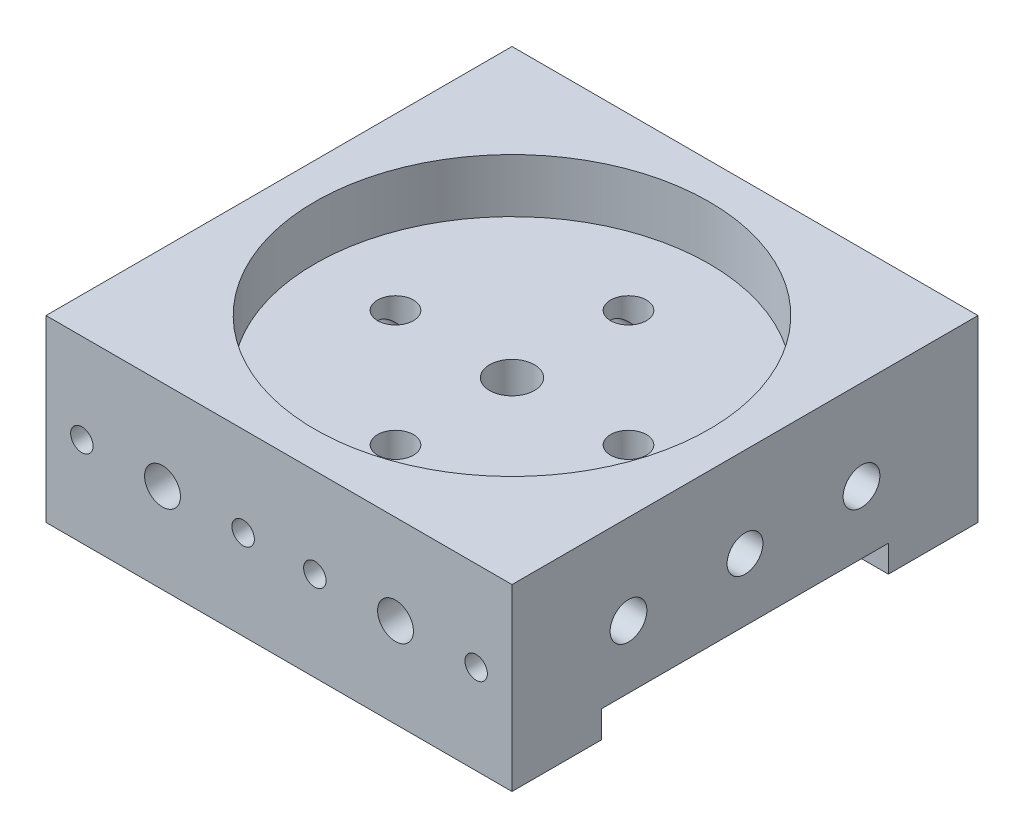
SolidWorks part; units mm, degrees
ref_plane "Front Plane" through (0, 0, 0) normal (0, 0, 1) x (1, 0, 0)
ref_plane "Top Plane" through (0, 0, 0) normal (0, 1, 0) x (1, 0, 0)
ref_plane "Right Plane" through (0, 0, 0) normal (1, 0, 0) x (0, 0, -1)
sketch "Base Block Sketch" plane through (0, 0, 0) normal (0, 1, 0) x (1, 0, 0)
  line L1 (-13, -13) -> (13, -13)
  line L2 (-13, -13) -> (-13, 13)
  line L3 (-13, 13) -> (13, 13)
  line L4 (13, -13) -> (13, 13)
  line L5 (-13, -13) -> (13, 13) construction
  line L6 (-13, 13) -> (13, -13) construction
  point P0 (0, 0)
  dimension "D2" = 13
extrude "Base Block Extrude" add sketch "Base Block Sketch" along normal blind 10
sketch "Top Circular Cut Sketch" plane through (0, 0, 0) normal (0, 1, 0) x (1, 0, 0)
  circle A0 centre (0, 0) radius 11
  dimension "D1" = 22
extrude "Top Circular Cut" cut sketch "Top Circular Cut Sketch" against normal blind 3 from surface starting at face at (0, 10, 0)
sketch "Bottom Slot Sketch" plane through (0, 0, 0) normal (0, 1, 0) x (1, 0, 0)
  line L0 (13, -13) -> (13, 13) construction
  line L1 (-13, -8) -> (13, -8)
  line L2 (-13, -8) -> (-13, 8)
  line L3 (-13, 8) -> (13, 8)
  line L4 (13, -8) -> (13, 8)
  line L5 (-13, -8) -> (13, 8) construction
  line L6 (-13, 8) -> (13, -8) construction
  point P0 (0, 0)
  dimension "D1" = 16
extrude "Bottom Slot Cut" cut sketch "Bottom Slot Sketch" along normal blind 1.5
sketch "3 Large Hole Positions Right Plane" plane through (0, 0, 0) normal (1, 0, 0) x (0, 0, -1)
  line L0 (-13, 10) -> (-13, 0) construction
  line L1 (-13, 10) -> (13, 10) construction
  point P0 (-6.5, 5)
  point P1 (0, 5)
  point P2 (6.5, 5)
  dimension "D1" = 13
  dimension "D2" = 13
  dimension "D3" = 5
  dimension "D4" = 6.5
sketch "6 Hole Positions Front Plane" plane through (0, 0, 0) normal (0, 0, 1) x (1, 0, 0)
  line L0 (-13, 0) -> (13, 0) construction
  line L1 (13, 10) -> (13, 0) construction
  line L2 (-13, 10) -> (-13, 0) construction
  point P0 (-11, 5)
  point P1 (-6.5, 5)
  point P2 (-2, 5)
  point P3 (2, 5)
  point P4 (6.5, 5)
  point P5 (11, 5)
  dimension "D1" = 5
  dimension "D2" = 9
  dimension "D3" = 9
  dimension "D4" = 6.5
  dimension "D5" = 6.5
  dimension "D6" = 4.5
  dimension "D7" = 4.5
sketch "5 Hole Positions in Circle Top Plane" plane through (0, 0, 0) normal (0, 1, 0) x (1, 0, 0)
  point P0 (0, 0)
  point P1 (6.5, 0)
  point P3 (-6.5, 0)
  point P5 (0, 6.5)
  point P6 (0, -6.5)
  dimension "D1" = 13
  dimension "D2" = 13
  dimension "D3" = 6.5
  dimension "D4" = 6.5
hole_wizard "M1.6x0.35 Tapped Hole3" positions "Sketch47" profile "Sketch48" tap size "M1.6x0.35" standard "ANSI Metric"
sketch "Sketch47" plane through (0, 0, 13) normal (0, 0, 1) x (1, 0, 0)
  point P0 (-11, 5)
  point P3 (-2, 5)
  point P6 (2, 5)
  point P9 (11, 5)
sketch "Sketch48" plane through (-11, 5, 13) normal (1, 0, 0) x (0, -1, 0)
  line L0 (0, 0) -> (0, 4.3755)
  line L1 (0, 4.3755) -> (0.625, 4)
  line L2 (0.625, 4) -> (0.625, 0)
  line L5 (0.625, 0) -> (0, 0)
  line L10 (0, 4.3755) -> (-0.625, 4) construction
  line L11 (0, -6.35) -> (0, 107.95) construction
  dimension "Tap Drill Dia." = 1.25
  dimension "Tap Drill Depth" = 4
  dimension "Drill Angle" = 118
cosmetic thread "Hole Thread6" parameters "D1"=3.2, "D2"=1.6
cosmetic thread "Hole Thread7" parameters "D1"=3.2, "D2"=1.6
cosmetic thread "Hole Thread8" parameters "D1"=3.2, "D2"=1.6
cosmetic thread "Hole Thread9" parameters "D1"=3.2, "D2"=1.6
hole_wizard "M1.6x0.35 Tapped Hole4" positions "Sketch49" profile "Sketch50" tap size "M1.6x0.35" standard "ANSI Metric"
sketch "Sketch49" plane through (0, 0, -13) normal (0, 0, -1) x (-1, 0, 0)
  point P0 (-11, 5)
  point P3 (-2, 5)
  point P6 (2, 5)
  point P9 (11, 5)
sketch "Sketch50" plane through (11, 5, -13) normal (1, 0, 0) x (0, 1, 0)
  line L0 (0, 0) -> (0, 4.3755)
  line L1 (0, 4.3755) -> (0.625, 4)
  line L2 (0.625, 4) -> (0.625, 0)
  line L5 (0.625, 0) -> (0, 0)
  line L10 (0, 4.3755) -> (-0.625, 4) construction
  line L11 (0, -6.35) -> (0, 107.95) construction
  dimension "Tap Drill Dia." = 1.25
  dimension "Tap Drill Depth" = 4
  dimension "Drill Angle" = 118
cosmetic thread "Hole Thread10" parameters "D1"=3.2, "D2"=1.6
cosmetic thread "Hole Thread11" parameters "D1"=3.2, "D2"=1.6
cosmetic thread "Hole Thread12" parameters "D1"=3.2, "D2"=1.6
cosmetic thread "Hole Thread13" parameters "D1"=3.2, "D2"=1.6
hole_wizard "Ø2.0 (2) Diameter Hole1" positions "Sketch16" profile "Sketch17" hole size "Ø2.0" standard "ANSI Metric"
sketch "Sketch16" plane through (0, 0, 13) normal (0, 0, 1) x (1, 0, 0)
  point P0 (-6.5, 5)
  point P3 (6.5, 5)
sketch "Sketch17" plane through (-6.5, 5, 13) normal (1, 0, 0) x (0, -1, 0)
  line L0 (0, 0) -> (0, 8.6009)
  line L1 (0, 8.6009) -> (1, 8)
  line L2 (1, 8) -> (1, 0)
  line L5 (1, 0) -> (0, 0)
  line L10 (0, 8.6009) -> (-1, 8) construction
  line L11 (0, -6.35) -> (0, 107.95) construction
  dimension "Hole Dia." = 2
  dimension "Hole Depth" = 8
  dimension "Drill Angle" = 118
hole_wizard "Ø2.0 (2) Diameter Hole2" positions "Sketch18" profile "Sketch19" hole size "Ø2.0" standard "ANSI Metric"
sketch "Sketch18" plane through (0, 0, -13) normal (0, 0, -1) x (-1, 0, 0)
  point P0 (-6.5, 5)
  point P3 (6.5, 5)
sketch "Sketch19" plane through (6.5, 5, -13) normal (1, 0, 0) x (0, 1, 0)
  line L0 (0, 0) -> (0, 8.6009)
  line L1 (0, 8.6009) -> (1, 8)
  line L2 (1, 8) -> (1, 0)
  line L5 (1, 0) -> (0, 0)
  line L10 (0, 8.6009) -> (-1, 8) construction
  line L11 (0, -6.35) -> (0, 107.95) construction
  dimension "Hole Dia." = 2
  dimension "Hole Depth" = 8
  dimension "Drill Angle" = 118
hole_wizard "Ø2.0 (2) Diameter Hole11" positions "Sketch39" profile "Sketch40" hole size "Ø2.0" standard "ANSI Metric" end condition through all
sketch "Sketch39" plane through (0, 7, 0) normal (0, 1, 0) x (1, 0, 0)
  point P0 (-6.5, 0)
  point P3 (0, -6.5)
  point P6 (6.5, 0)
  point P9 (0, 6.5)
sketch "Sketch40" plane through (-6.5, 7, 0) normal (1, 0, 0) x (0, 0, 1)
  line L0 (0, 0) -> (0, 7)
  line L1 (0, 7) -> (1, 7)
  line L2 (1, 7) -> (1, 0)
  line L5 (1, 0) -> (0, 0)
  line L11 (0, -6.35) -> (0, 107.95) construction
  dimension "Thru Hole Dia." = 2
  dimension "Thru Hole Depth" = 7
hole_wizard "M3x0.5 Tapped Hole1" positions "Sketch41" profile "Sketch42" tap size "M3x0.5" standard "ANSI Metric"
sketch "Sketch41" plane through (0, 7, 0) normal (0, 1, 0) x (1, 0, 0)
  point P0 (0, 0)
sketch "Sketch42" plane through (0, 7, 0) normal (1, 0, 0) x (0, 0, 1)
  line L0 (0, 0) -> (0, 4.7511)
  line L1 (0, 4.7511) -> (1.25, 4)
  line L2 (1.25, 4) -> (1.25, 0)
  line L5 (1.25, 0) -> (0, 0)
  line L10 (0, 4.7511) -> (-1.25, 4) construction
  line L11 (0, -6.35) -> (0, 107.95) construction
  dimension "Tap Drill Dia." = 2.5
  dimension "Tap Drill Depth" = 4
  dimension "Drill Angle" = 118
cosmetic thread "Hole Thread1" parameters "D1"=6, "D2"=3
hole_wizard "M2.5x0.45 Tapped Hole2" positions "Sketch51" profile "Sketch52" tap size "M2.5x0.45" standard "ANSI Metric"
sketch "Sketch51" plane through (13, 0, 0) normal (1, 0, 0) x (0, 0, -1)
  point P0 (-6.5, 5)
sketch "Sketch52" plane through (13, 5, 6.5) normal (0, 1, 0) x (0, 0, -1)
  line L0 (0, 0) -> (0, 13.6159)
  line L1 (0, 13.6159) -> (1.025, 13)
  line L2 (1.025, 13) -> (1.025, 0)
  line L5 (1.025, 0) -> (0, 0)
  line L10 (0, 13.6159) -> (-1.025, 13) construction
  line L11 (0, -6.35) -> (0, 107.95) construction
  dimension "Tap Drill Dia." = 2.05
  dimension "Tap Drill Depth" = 13
  dimension "Drill Angle" = 118
cosmetic thread "Hole Thread14" parameters "D1"=5, "D2"=2.5
hole_wizard "M2.5x0.45 Tapped Hole3" positions "Sketch53" profile "Sketch54" tap size "M2.5x0.45" standard "ANSI Metric"
sketch "Sketch53" plane through (-13, 0, 0) normal (-1, 0, 0) x (0, 0, 1)
  point P0 (-6.5, 5)
sketch "Sketch54" plane through (-13, 5, -6.5) normal (0, 1, 0) x (0, 0, 1)
  line L0 (0, 0) -> (0, 13.6159)
  line L1 (0, 13.6159) -> (1.025, 13)
  line L2 (1.025, 13) -> (1.025, 0)
  line L5 (1.025, 0) -> (0, 0)
  line L10 (0, 13.6159) -> (-1.025, 13) construction
  line L11 (0, -6.35) -> (0, 107.95) construction
  dimension "Tap Drill Dia." = 2.05
  dimension "Tap Drill Depth" = 13
  dimension "Drill Angle" = 118
cosmetic thread "Hole Thread15" parameters "D1"=5, "D2"=2.5
hole_wizard "M2.5x0.45 Tapped Hole4" positions "Sketch55" profile "Sketch56" tap size "M2.5x0.45" standard "ANSI Metric"
sketch "Sketch55" plane through (13, 0, 0) normal (1, 0, 0) x (0, 0, -1)
  point P0 (6.5, 5)
sketch "Sketch56" plane through (13, 5, -6.5) normal (0, 1, 0) x (0, 0, -1)
  line L0 (0, 0) -> (0, 7.1159)
  line L1 (0, 7.1159) -> (1.025, 6.5)
  line L2 (1.025, 6.5) -> (1.025, 0)
  line L5 (1.025, 0) -> (0, 0)
  line L10 (0, 7.1159) -> (-1.025, 6.5) construction
  line L11 (0, -6.35) -> (0, 107.95) construction
  dimension "Tap Drill Dia." = 2.05
  dimension "Tap Drill Depth" = 6.5
  dimension "Drill Angle" = 118
cosmetic thread "Hole Thread16" parameters "D1"=5, "D2"=2.5
hole_wizard "M2.5x0.45 Tapped Hole5" positions "Sketch57" profile "Sketch58" tap size "M2.5x0.45" standard "ANSI Metric"
sketch "Sketch57" plane through (-13, 0, 0) normal (-1, 0, 0) x (0, 0, 1)
  point P0 (6.5, 5)
sketch "Sketch58" plane through (-13, 5, 6.5) normal (0, 1, 0) x (0, 0, 1)
  line L0 (0, 0) -> (0, 7.1159)
  line L1 (0, 7.1159) -> (1.025, 6.5)
  line L2 (1.025, 6.5) -> (1.025, 0)
  line L5 (1.025, 0) -> (0, 0)
  line L10 (0, 7.1159) -> (-1.025, 6.5) construction
  line L11 (0, -6.35) -> (0, 107.95) construction
  dimension "Tap Drill Dia." = 2.05
  dimension "Tap Drill Depth" = 6.5
  dimension "Drill Angle" = 118
cosmetic thread "Hole Thread17" parameters "D1"=5, "D2"=2.5
hole_wizard "Ø2.0 (2) Diameter Hole5" positions "Sketch26" profile "Sketch27" hole size "Ø2.0" standard "ANSI Metric"
sketch "Sketch26" plane through (13, 0, 0) normal (1, 0, 0) x (0, 0, -1)
  point P0 (-6.5, 5)
  point P3 (0, 5)
sketch "Sketch27" plane through (13, 5, 6.5) normal (0, 1, 0) x (0, 0, -1)
  line L0 (0, 0) -> (0, 7.1009)
  line L1 (0, 7.1009) -> (1, 6.5)
  line L2 (1, 6.5) -> (1, 0)
  line L5 (1, 0) -> (0, 0)
  line L10 (0, 7.1009) -> (-1, 6.5) construction
  line L11 (0, -6.35) -> (0, 107.95) construction
  dimension "Hole Dia." = 2
  dimension "Hole Depth" = 6.5
  dimension "Drill Angle" = 118
hole_wizard "Ø2.0 (2) Diameter Hole6" positions "Sketch28" profile "Sketch29" hole size "Ø2.0" standard "ANSI Metric"
sketch "Sketch28" plane through (-13, 0, 0) normal (-1, 0, 0) x (0, 0, 1)
  point P0 (-6.5, 5)
  point P3 (0, 5)
sketch "Sketch29" plane through (-13, 5, -6.5) normal (0, 1, 0) x (0, 0, 1)
  line L0 (0, 0) -> (0, 7.1009)
  line L1 (0, 7.1009) -> (1, 6.5)
  line L2 (1, 6.5) -> (1, 0)
  line L5 (1, 0) -> (0, 0)
  line L10 (0, 7.1009) -> (-1, 6.5) construction
  line L11 (0, -6.35) -> (0, 107.95) construction
  dimension "Hole Dia." = 2
  dimension "Hole Depth" = 6.5
  dimension "Drill Angle" = 118
sketch "Bottom Plate Securing Holes" plane through (0, 0, 0) normal (0, 1, 0) x (1, 0, 0)
  line L0 (13, 8) -> (-13, 8) construction
  line L1 (-3, 4) -> (3, 4) construction
  line L2 (-3, 4) -> (-3, -4) construction
  line L3 (-3, -4) -> (3, -4) construction
  line L4 (3, 4) -> (3, -4) construction
  line L5 (-3, 4) -> (3, -4) construction
  line L6 (-3, -4) -> (3, 4) construction
  line L7 (13, 8) -> (13, 13) construction
  point P0 (0, 0)
  dimension "D1" = 4
  dimension "D2" = 10
hole_wizard "M1.6x0.35 Tapped Hole5" positions "Sketch65" profile "Sketch66" tap size "M1.6x0.35" standard "ANSI Metric"
sketch "Sketch65" plane through (0, 1.5, 0) normal (0, -1, 0) x (-1, 0, 0)
  point P0 (3, 4)
  point P3 (-3, -4)
sketch "Sketch66" plane through (-3, 1.5, -4) normal (1, 0, 0) x (0, 0, -1)
  line L0 (0, 0) -> (0, 3.3755)
  line L1 (0, 3.3755) -> (0.625, 3)
  line L2 (0.625, 3) -> (0.625, 0)
  line L5 (0.625, 0) -> (0, 0)
  line L10 (0, 3.3755) -> (-0.625, 3) construction
  line L11 (0, -6.35) -> (0, 107.95) construction
  dimension "Tap Drill Dia." = 1.25
  dimension "Tap Drill Depth" = 3
  dimension "Drill Angle" = 118
cosmetic thread "Hole Thread18" parameters "D1"=3.2, "D2"=1.6
cosmetic thread "Hole Thread19" parameters "D1"=3.2, "D2"=1.6
sketch "4 Bottom Hole Positions" plane through (0, 0, 0) normal (0, 1, 0) x (1, 0, 0)
  line L1 (-6.5, 4) -> (6.5, 4) construction
  line L2 (-6.5, 4) -> (-6.5, -4) construction
  line L3 (-6.5, -4) -> (6.5, -4) construction
  line L4 (6.5, 4) -> (6.5, -4) construction
  line L5 (-6.5, 4) -> (6.5, -4) construction
  line L6 (-6.5, -4) -> (6.5, 4) construction
  point P0 (0, 0)
  point P6 (0, 0)
  point P7 (0, 0)
hole_wizard "Ø2.0mm Dowel Hole1" positions "Sketch67" profile "Sketch68" hole size "Ø2.0" standard "ANSI Metric"
sketch "Sketch67" plane through (0, 1.5, 0) normal (0, -1, 0) x (-1, 0, 0)
  point P0 (6.5, 4)
  point P3 (6.5, -4)
  point P6 (-6.5, -4)
  point P9 (-6.5, 4)
sketch "Sketch68" plane through (-6.5, 1.5, -4) normal (1, 0, 0) x (0, 0, -1)
  line L0 (0, 0) -> (0, 4.6009)
  line L1 (0, 4.6009) -> (1, 4)
  line L2 (1, 4) -> (1, 0)
  line L5 (1, 0) -> (0, 0)
  line L10 (0, 4.6009) -> (-1, 4) construction
  line L11 (0, -6.35) -> (0, 107.95) construction
  dimension "Hole Dia." = 2
  dimension "Hole Depth" = 4
  dimension "Drill Angle" = 118
sketch "2 Bracket Hole Positions" plane through (0, 0, 0) normal (0, 1, 0) x (1, 0, 0)
  line L0 (-13, 13) -> (-13, -13) construction
  line L1 (-13, -8) -> (13, -8) construction
  line L2 (13, 13) -> (-13, 13) construction
  point P0 (-9.5, 10.5)
  point P1 (-9.5, -10.5)
  dimension "D1" = 3.5
  dimension "D2" = 2.5
  dimension "D3" = 2.5
hole_wizard "M1.6x0.35 Tapped Hole7" positions "Sketch73" profile "Sketch74" tap size "M1.6x0.35" standard "ANSI Metric"
sketch "Sketch73" plane through (0, 0, 0) normal (0, -1, 0) x (-1, 0, 0)
  point P0 (9.5, -10.5)
  point P5 (9.5, 10.5)
sketch "Sketch74" plane through (-9.5, 0, 10.5) normal (1, 0, 0) x (0, 0, -1)
  line L0 (0, 0) -> (0, 3.3755)
  line L1 (0, 3.3755) -> (0.625, 3)
  line L2 (0.625, 3) -> (0.625, 0)
  line L5 (0.625, 0) -> (0, 0)
  line L10 (0, 3.3755) -> (-0.625, 3) construction
  line L11 (0, -6.35) -> (0, 107.95) construction
  dimension "Tap Drill Dia." = 1.25
  dimension "Tap Drill Depth" = 3
  dimension "Drill Angle" = 118
cosmetic thread "Hole Thread22" parameters "D1"=3.2, "D2"=1.6
cosmetic thread "Hole Thread23" parameters "D1"=3.2, "D2"=1.6
